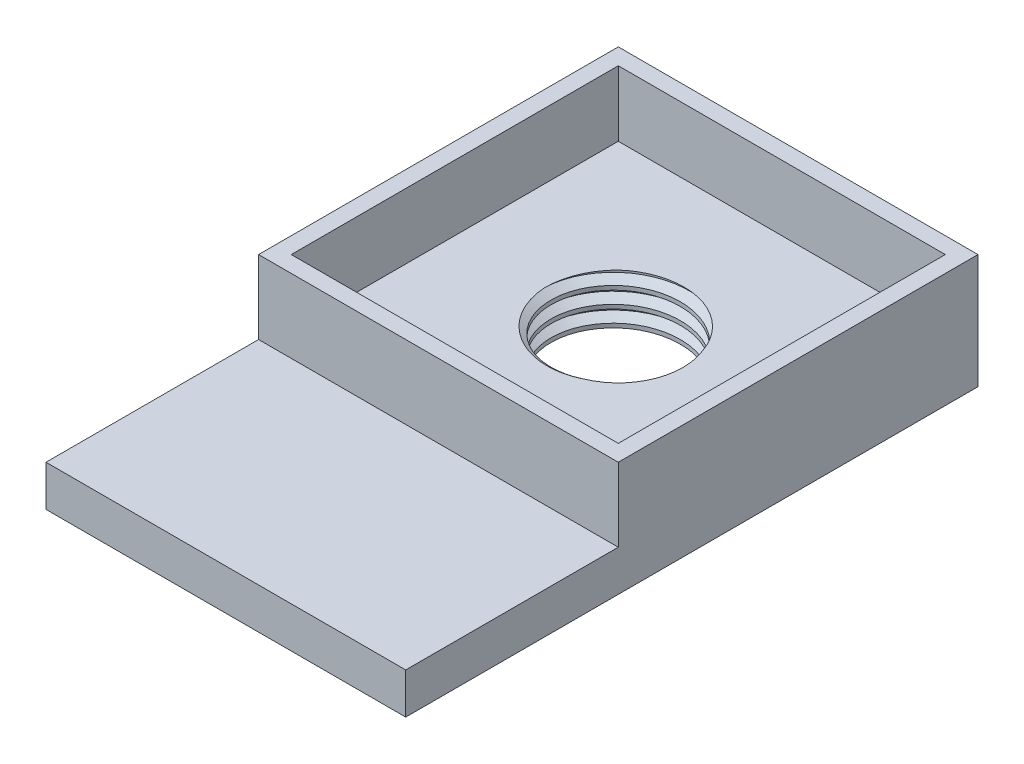
SolidWorks part; units mm, degrees
note: The reader was unsure of these and kept them because the rebuilt part matched: shared geometry of "Sketch1<2>", "Sketch2<3>".
ref_plane "Front Plane" through (0, 0, 0) normal (0, 0, 1) x (1, 0, 0)
ref_plane "Top Plane" through (0, 0, 0) normal (0, 1, 0) x (1, 0, 0)
ref_plane "Right Plane" through (0, 0, 0) normal (1, 0, 0) x (0, 0, -1)
sketch "Sketch1" plane through (0, 0, 0) normal (0, 1, 0) x (1, 0, 0)
  line L1 (-10, -10) -> (10, -10)
  line L2 (-10, -10) -> (-10, 10)
  line L3 (-10, 10) -> (10, 10)
  line L4 (10, -10) -> (10, 10)
  line L5 (-10, -10) -> (10, 10) construction
  line L6 (-10, 10) -> (10, -10) construction
  line L7 (-11, -11) -> (11, -11)
  line L8 (-11, -11) -> (-11, 11)
  line L9 (-11, 11) -> (11, 11)
  line L10 (11, -11) -> (11, 11)
  line L11 (-11, -11) -> (11, 11) construction
  line L12 (-11, 11) -> (11, -11) construction
  point P0 (0, 0)
  point P6 (0, 0)
  dimension "D1" = 20
  dimension "D2" = 20
  dimension "D3" = 22
  dimension "D4" = 22
extrude "Boss-Extrude1" add sketch "Sketch1" along normal blind 5 and the other way blind 2
extrude "Boss-Extrude2" add sketch "Sketch1<2>" along normal blind 1 and the other way blind 2 contours L1 L4 L3 L2
sketch "Sketch1<2>" plane through (0, 0, 0) normal (0, 1, 0) x (1, 0, 0) same geometry as "Sketch1"
sketch "Sketch2" plane through (0, -2, 0) normal (0, -1, 0) x (1, 0, 0)
  circle A0 centre (0, 0) radius 4.5
  circle A1 centre (0, 0) radius 7
  dimension "D1" = 9
extrude "Cut-Extrude1" cut sketch "Sketch2<3>" against normal blind 7 contours A0
sketch "Sketch2<3>" plane through (0, -2, 0) normal (0, -1, 0) x (1, 0, 0) same geometry as "Sketch2"
sketch "Sketch3" plane through (0, 0, 0) normal (0, 1, 0) x (1, 0, 0)
  line L0 (0, -11) -> (0, -24)
  line L1 (-11, -11) -> (11, -11)
  line L2 (-11, -11) -> (-11, -24)
  line L3 (-11, -24) -> (11, -24)
  line L4 (11, -11) -> (11, -24)
  line L5 (-10.75, -24) -> (0, -24)
  line L6 (-8, -20) -> (-8, -24)
  line L7 (-10.75, -24) -> (-9.9027, -24)
  line L8 (-8, -20) -> (8, -20)
  line L9 (-8, -24) -> (8, -24)
  line L10 (-10.75, -24) -> (-13.75, -24)
  line L11 (0, -24) -> (-2.0006, -24)
  line L12 (0, -24) -> (-1, -24)
  line L13 (-11, 11) -> (-11, -11) construction
  line L14 (-1, -24) -> (-1, -21.75)
  line L15 (0, -24) -> (-3, -24)
  line L16 (10.75, -24) -> (13.75, -24)
  line L17 (8, -20) -> (8, -24)
  line L18 (-8, -20) -> (8, -24) construction
  line L19 (-8, -24) -> (8, -20) construction
  line L20 (-11, -9) -> (-11, -11)
  line L21 (11, -9) -> (11, -11)
  line L22 (10.75, -24) -> (0, -24)
  line L23 (-8, -20) -> (-3, -24)
  line L24 (1, -24) -> (1, -21.75)
  line L25 (8, -20) -> (3, -24)
  spline S0 degree 1 poles (-8, -20) (-1, -21.75) knots 0 0 1 1
  spline S1 degree 1 poles (8, -20) (1, -21.75) knots 0 0 1 1
  point P9 (0, -22)
  dimension "D1" = 10.75
  dimension "D3" = 13
  dimension "D4" = 3
  dimension "D5" = 4
  dimension "D9" = 0
extrude "Boss-Extrude3" add sketch "Sketch3" against normal blind 2 contours L8 L17 L3 L4 L1 L0 | L6 L8 L0 L1 L2 L3 L5 | L8 S0 L14 L11 L0 | S0 L23 L9 L14 | L23 L6 L5 | S1 L8 L0 L3 L24 | L25 S1 L24 L22 | L17 L25 L3
thread "Thread2" pitch 1 start angle 0, offset 1, length 10, pitch 1, diameter 9
ref_plane "Plane3" through (-4.5, 2, 0) normal (0, 0, 1) x (-1, 0, 0)
sketch "Thread Profile3" plane through (-4.5, 2, 0) normal (0, 0, 1) x (-1, 0, 0)
  line L0 (0, 0) -> (0, 1) construction
  line L11 (0, 0) -> (0, 0.875)
  line L12 (0, 0.875) -> (-0.5413, 0.5625)
  line L13 (-0.5413, 0.5625) -> (-0.5413, 0.3125)
  line L15 (-0.5413, 0.3125) -> (0, 0)
  line L17 (-0.5413, 0.4375) -> (0, 0.4375) construction
  point P2 (0, 0)
  dimension "Pitch" = 1
  dimension "Profile_Angle" = 60
  dimension "Profile_Land" = 0.25
  dimension "Profile_Height" = 0.5413
sketch "Sketch20" plane through (0, 0, 0) normal (0, 1, 0) x (1, 0, 0)
  line L1 (-11, -11) -> (11, -11)
  line L2 (-11, -11) -> (-11, -24)
  line L3 (-11, -24) -> (11, -24)
  line L4 (11, -11) -> (11, -24)
extrude "Boss-Extrude4" add sketch "Sketch20" along normal blind 0.5
